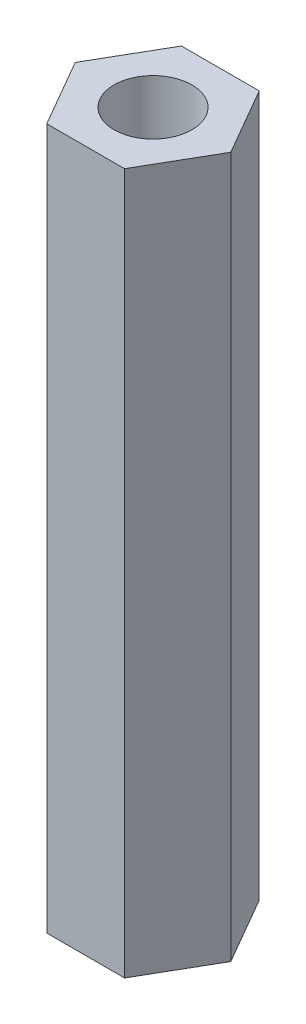
SolidWorks part; units mm, degrees
ref_plane "Front Plane" through (0, 0, 0) normal (0, 0, 1) x (1, 0, 0)
ref_plane "Top Plane" through (0, 0, 0) normal (0, 1, 0) x (1, 0, 0)
ref_plane "Right Plane" through (0, 0, 0) normal (1, 0, 0) x (0, 0, -1)
sketch "Sketch1" plane through (0, 0, 0) normal (0, 1, 0) x (1, 0, 0)
  line L1 (2.996, 0) -> (1.498, 2.5946)
  line L2 (1.498, 2.5946) -> (-1.498, 2.5946)
  line L3 (-1.498, 2.5946) -> (-2.996, 0)
  line L4 (-2.996, 0) -> (-1.498, -2.5946)
  line L5 (-1.498, -2.5946) -> (1.498, -2.5946)
  line L6 (1.498, -2.5946) -> (2.996, 0)
  circle A0 centre (0, 0) radius 1.5
  circle A1 centre (0, 0) radius 2.5946 construction
extrude "Boss-Extrude1" add sketch "Sketch1" along normal blind 27
